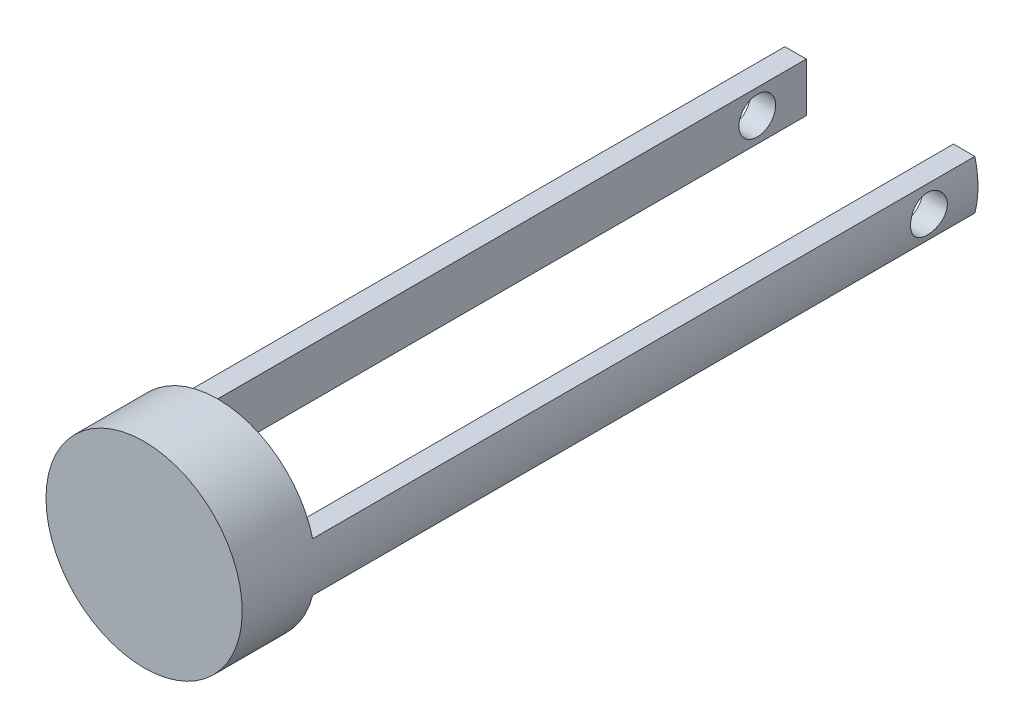
SolidWorks part; units mm, degrees
material "1060 Alloy"
ref_plane "Front Plane" through (0, 0, 0) normal (0, 0, 1) x (1, 0, 0)
ref_plane "Top Plane" through (0, 0, 0) normal (0, 1, 0) x (1, 0, 0)
ref_plane "Right Plane" through (0, 0, 0) normal (1, 0, 0) x (0, 0, -1)
sketch "Sketch1" plane through (0, 0, 0) normal (0, 0, 1) x (1, 0, 0)
  line L0 (49.1869, 12.7) -> (38.1, 12.7)
  line L1 (38.1, 12.7) -> (38.1, -12.7)
  line L2 (38.1, -12.7) -> (49.1869, -12.7)
  line L3 (-49.1869, 12.7) -> (-38.1, 12.7)
  line L4 (-38.1, 12.7) -> (-38.1, -12.7)
  line L5 (-38.1, -12.7) -> (-49.1869, -12.7)
  circle A0 centre (0, 0) radius 50.8
  dimension "D1" = 101.6
  dimension "D2" = 12.7
  dimension "D3" = 25.4
extrude "Boss-Extrude1" add sketch "Sketch1" against normal blind 38.1 contours L0 A0 L3 L4 L5 L2 L1 region at (0, 0, 0)
extrude "Boss-Extrude2" add sketch "Sketch1<3>" against normal blind 381 contours L3 A0 L5 L4 | L2 A0 L0 L1 region at (44.1923, 0, 0) region at (-44.1923, 0, 0)
sketch "Sketch1<3>" plane through (0, 0, 0) normal (0, 0, 1) x (1, 0, 0) same geometry as "Sketch1"
sketch "Sketch2" plane through (-38.1, 0, 0) normal (1, 0, 0) x (0, 0, -1)
  line L0 (0, 50.8) -> (0, -50.8) construction
  line L1 (381, 12.7) -> (38.1, 12.7) construction
  circle A0 centre (355.6, 0) radius 9.525
  dimension "D1" = 19.05
  dimension "D2" = 355.6
  dimension "D3" = 12.7
extrude "Cut-Extrude1" cut sketch "Sketch2" against normal through all both and the other way through all
